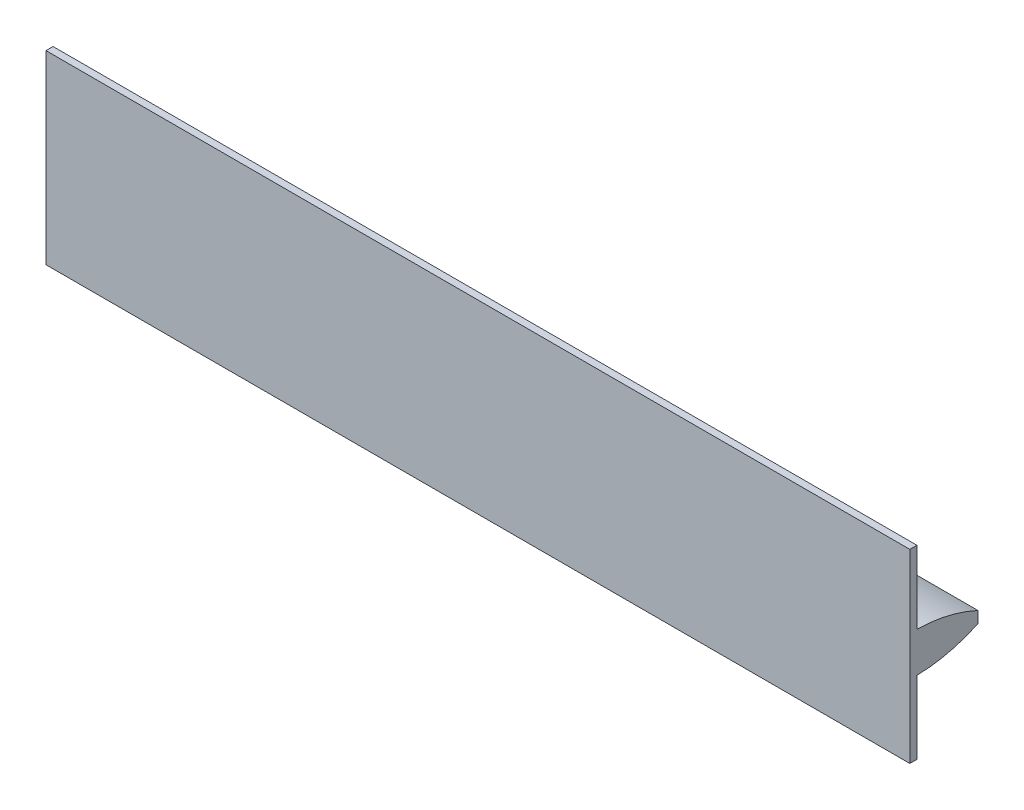
SolidWorks part; units mm, degrees
ref_plane "Front Plane" through (0, 0, 0) normal (0, 0, 1) x (1, 0, 0)
ref_plane "Top Plane" through (0, 0, 0) normal (0, 1, 0) x (1, 0, 0)
ref_plane "Right Plane" through (0, 0, 0) normal (1, 0, 0) x (0, 0, -1)
sketch "Sketch1" plane through (0, 0, 0) normal (1, 0, 0) x (0, 0, -1)
  line L0 (0, 0) -> (59.4881, 0)
  line L1 (55, 0) -> (-55, 0) construction
  line L2 (59.4881, 0) -> (59.4881, 3.175)
  line L3 (59.4881, 3.175) -> (16.3081, 3.175)
  line L4 (16.3081, 3.175) -> (0, 3.175) construction
  line L5 (0, 55) -> (0, -55) construction
  line L6 (59.4881, 1.5875) -> (0, 1.5875) construction
  line L7 (0, 0) -> (0, 124.5585) construction
  line L8 (-3.175, -10.4951) -> (-3.175, 72.3911) construction
  line L9 (-6.35, 0) -> (-6.35, 124.5585) construction
  line L10 (-65.8381, 1.5875) -> (-6.35, 1.5875) construction
  line L11 (-22.6581, 3.175) -> (-6.35, 3.175) construction
  line L12 (-65.8381, 3.175) -> (-22.6581, 3.175)
  line L13 (-65.8381, 0) -> (-65.8381, 3.175)
  line L14 (-6.35, 0) -> (-65.8381, 0)
  line L15 (-6.35, 51.2862) -> (0, 51.2862)
  line L16 (-6.35, 0) -> (0, 0)
  arc A0 (16.3081, 3.175) -> (0, 51.2862) centre (-67.4969, 1.5875) ccw
  arc A1 (-22.6581, 3.175) -> (-6.35, 51.2862) centre (61.1469, 1.5875) cw
  dimension "D2" = 83.82
  dimension "D1" = 3.175
  dimension "D3" = 50.8
  dimension "D4" = 43.18
  dimension "D5" = 6.35
extrude "Boss-Extrude1" [suppressed] add sketch "Sketch1" against normal blind 482.6
sketch "Sketch2" plane through (0, 0, 0) normal (1, 0, 0) x (0, 0, -1)
  line L0 (0, 0) -> (0, 51.8065)
  line L1 (0, 55) -> (0, -55) construction
  line L2 (0, 51.8065) -> (3.9688, 51.8065)
  line L3 (3.9688, 51.8065) -> (3.9688, 11.1515)
  line L4 (0, 0) -> (38.1, 0)
  line L5 (55, 0) -> (-55, 0) construction
  line L6 (38.1, 0) -> (38.1, 3.175)
  line L7 (0.7937, 61.624) -> (0.7938, -152.4777) construction
  line L8 (2.3812, 62.5054) -> (2.3813, -144.1659) construction
  line L9 (0.7937, 57.434) -> (3.9687, 57.434) construction
  line L10 (2.3813, 11.1665) -> (27.3868, 11.1665) construction
  arc A0 (3.9688, 11.1515) -> (38.1, 3.175) centre (2.3813, -72.6535) cw
  arc A1 (3.9688, 11.1515) -> (2.3813, 11.1665) centre (2.3813, -72.6535) ccw construction
  point P18 (2.3812, 57.434)
  dimension "D6" = 83.82
  dimension "D1" = 38.1
  dimension "D2" = 124.46
  dimension "D3" = 3.9688
  dimension "D4" = 3.175
  dimension "D5" = 3.175
extrude "Boss-Extrude2" add sketch "Sketch2" against normal blind 482.6
mirror "Mirror1" about plane through (-482.6, 0, 0) normal (0, -1, 0) of "Boss-Extrude2"
